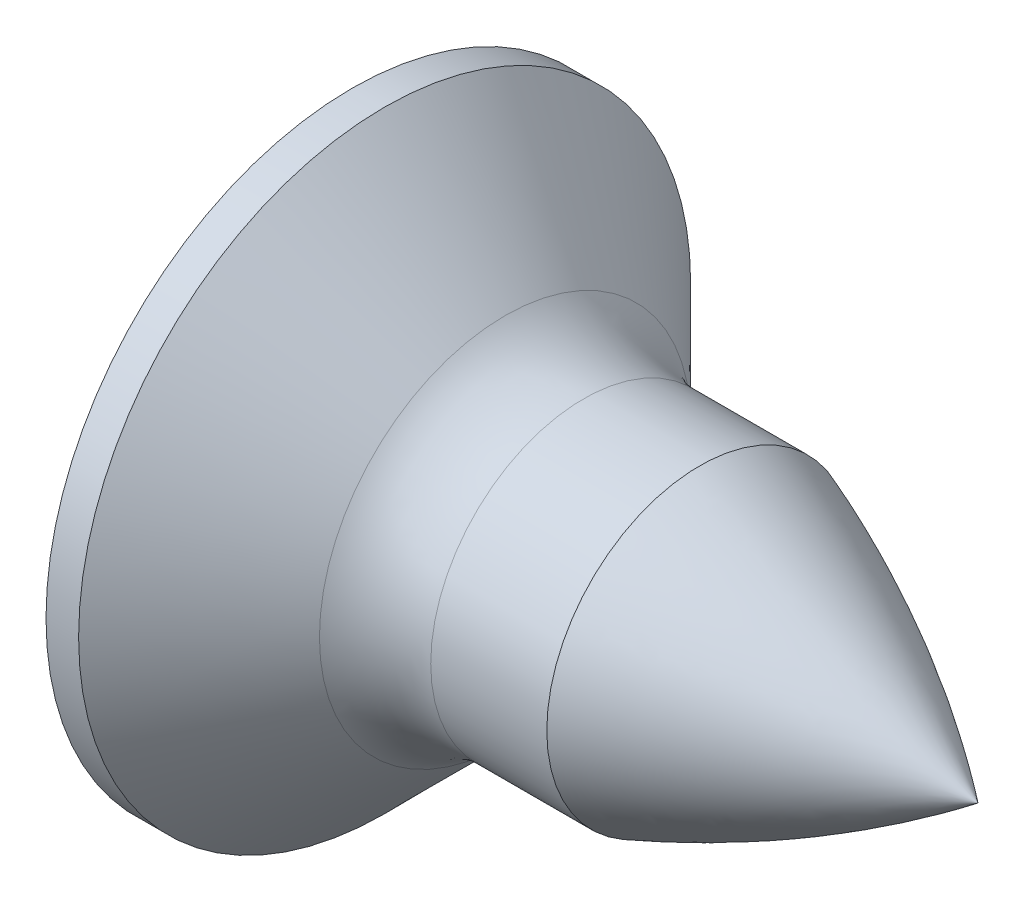
SolidWorks part; units mm, degrees
ref_plane "Front" through (0, 0, 0) normal (0, 0, 1) x (1, 0, 0)
ref_plane "Top" through (0, 0, 0) normal (0, 1, 0) x (1, 0, 0)
ref_plane "Right" through (0, 0, 0) normal (1, 0, 0) x (0, 0, -1)
sketch "Sketch1" plane through (0, 0, 0) normal (0, 0, 1) x (1, 0, 0)
  line L0 (-96.3852, 0) -> (11.3165, 0) construction
  line L1 (4.5, 0) -> (4.5, 1.1)
  line L2 (4.5, 1.1) -> (1.6657, 1.1)
  line L3 (1.9, 0.5946) -> (1.9, -0.97) construction
  line L4 (0.2343, 2.2) -> (0, 2.2)
  line L5 (4.5, 0) -> (0, 0)
  line L6 (1.1, 1.3343) -> (0.2343, 2.2)
  line L7 (0, 2.2) -> (0, 0)
  arc A0 (1.6657, 1.1) -> (1.1, 1.3343) centre (1.6657, 1.9) cw
  dimension "D1" = 45
  dimension "l" = 4.5
  dimension "k" = 1.1
revolve "Base" add sketch "Sketch1" angle 360 about L0
cosmetic thread "ThreadCosmetic1" [suppressed] parameters "D1"=2.6, "D2"=1.2
sketch "Sketch2" plane through (0, -0.7629, -8.3818) normal (-1, 0, 0) x (0, 0, 1)
  line L0 (2.3136, 0.7629) -> (16.8132, 0.7629) construction
  line L1 (8.3818, 3.0086) -> (8.3818, -8.9204) construction
  line L2 (8.5818, 1.7629) -> (8.1818, 1.7629)
  line L3 (8.1818, 1.7629) -> (8.1818, 0.9629)
  line L4 (8.1818, 0.9629) -> (7.3818, 0.9629)
  line L5 (7.3818, 0.9629) -> (7.3818, 0.5629)
  line L6 (8.1818, 0.5629) -> (7.3818, 0.5629)
  line L7 (8.1818, -0.2371) -> (8.1818, 0.5629)
  line L8 (8.5818, -0.2371) -> (8.1818, -0.2371)
  line L9 (8.5818, -0.2371) -> (8.5818, 0.5629)
  line L10 (8.5818, 0.5629) -> (9.3818, 0.5629)
  line L11 (9.3818, 0.9629) -> (9.3818, 0.5629)
  line L12 (8.5818, 0.9629) -> (9.3818, 0.9629)
  line L13 (8.5818, 1.7629) -> (8.5818, 0.9629)
  point P5 (9.3818, 0.7629)
  point P11 (7.3818, 0.7629)
  point P15 (8.3818, -0.2371)
  point P20 (8.3818, 1.7629)
  dimension "D1" = 0.4
extrude "CrossRecess" cut sketch "Sketch2" against normal blind 0.95
draft "Draft1" type of draft neutral plane draft angle 30 faces to draft 4 face at (0.475, -1, 0) face at (0.475, 0, 1) face at (0.475, 0, -1) face at (0.475, 1, 0) neutral plane through (0, 2.2, 0) neutral plane normal (-1, 0, 0) parameters "D1"=30
sketch "Sketch3" plane through (0, 0.5965, -8.6549) normal (-1, 0, 0) x (0, 0, 1)
  line L0 (8.6549, -0.5965) -> (16.919, 7.6677) construction
  line L2 (8.8549, -0.3965) -> (8.8549, -0.1965)
  line L4 (8.8549, -0.1965) -> (9.522, 0.2707)
  line L5 (9.0549, -0.3965) -> (9.522, 0.2707)
  line L6 (8.8549, -0.3965) -> (9.0549, -0.3965)
  line L7 (8.4549, -0.3965) -> (8.2549, -0.3965)
  line L8 (8.2549, -0.3965) -> (7.7877, 0.2707)
  line L9 (8.4549, -0.1965) -> (7.7877, 0.2707)
  line L10 (8.4549, -0.3965) -> (8.4549, -0.1965)
  line L11 (8.4549, -0.7965) -> (8.4549, -0.9965)
  line L12 (8.4549, -0.9965) -> (7.7877, -1.4636)
  line L13 (8.2549, -0.7965) -> (7.7877, -1.4636)
  line L14 (8.4549, -0.7965) -> (8.2549, -0.7965)
  line L15 (8.8549, -0.7965) -> (9.0549, -0.7965)
  line L16 (9.0549, -0.7965) -> (9.522, -1.4636)
  line L17 (8.8549, -0.9965) -> (9.522, -1.4636)
  line L18 (8.8549, -0.7965) -> (8.8549, -0.9965)
  line L19 (2.5867, -0.5965) -> (17.0862, -0.5965) construction
  line L20 (8.8549, -0.3965) -> (9.6549, -0.3965) construction
  line L22 (8.6549, 11.2261) -> (8.6549, -1) construction
  line L23 (10.9249, -0.5965) -> (-2.2894, -0.5965) construction
  dimension "D3" = 0.2
  dimension "D2" = 10
  dimension "D1" = 45
extrude "Cut-Extrude2" [suppressed] cut sketch "Sketch3" against normal up to surface (5.2 mm away) up to face at (0.95, 0, 0)
sketch "Sketch4" plane through (0, 0, 0) normal (0, 1, 0) x (1, 0, 0)
  line L0 (33.3282, 0) -> (18.3612, 0) construction
  line L2 (2.9, -1.1) -> (3.7, -1.1)
  line L3 (3.7, -1.1) -> (4.5, -0.9)
  line L5 (4.5, -1.1) -> (4.5, 1.1) construction
  line L6 (2.9, -1.1) -> (2.9, -1.6)
  line L7 (2.9, -1.6) -> (4.5, -1.6)
  line L8 (4.5, -1.6) -> (4.5, -0.9)
  point P15 (3.7, -1.1)
  dimension "D2" = 0.8
  dimension "D4" = 0.5
  dimension "D1" = 2.2
  dimension "D3" = 0.2
revolve "Cut-Revolve1" [suppressed] cut sketch "Sketch4" angle 360 about L0
sketch "Sketch5" plane through (0, 0, 0) normal (0, 1, 0) x (1, 0, 0)
  line L0 (34.7407, 0) -> (11.4121, 0) construction
  line L2 (4.5, -1.1) -> (4.5, 1.1) construction
  line L3 (4.5, 0) -> (2.5, -1.1) construction
  line L6 (4.5, 0) -> (5, 0)
  line L7 (2.5, -1.1) -> (4.5, -1.1)
  line L8 (5, 0) -> (5, -1.1)
  line L9 (5, -1.1) -> (4.5, -1.1)
  arc A0 (4.5, 0) -> (2.5, -1.1) centre (-0.3159, 6.388) cw
  dimension "D1" = 8
  dimension "D3" = 2.2
  dimension "D2" = 0.5
revolve "Cut-Revolve6" cut sketch "Sketch5" angle 360 about L0
sketch "Sketch6" plane through (0, 0, 0) normal (0, 0, 1) x (1, 0, 0)
  line L0 (1.65, 1.6) -> (2.15, 1.6)
  line L1 (2.15, 1.6) -> (2.15, 1.1)
  line L2 (2.15, 1.1) -> (1.9, 0.667)
  line L3 (1.9, 0.667) -> (1.65, 1.1)
  line L4 (1.65, 1.1) -> (1.65, 1.6)
  line L5 (0, 0) -> (5.5511, 0) construction
  line L7 (1.1, 1.3343) -> (1.1, -1.3343) construction
  dimension "D2" = 0.8
  dimension "D1" = 0.5
  dimension "D3" = 2.2
revolve "Cut-Revolve10" [suppressed] cut sketch "Sketch6" angle 360 about L5
pattern_linear "LPattern10" [suppressed] count 4 spacing 0.6 along (1, 0, 0) of bodies 110
equation "\"D3@Sketch4\" = \"yf@Sketch4\" / 8"
equation "\"D2@ThreadCosmetic1\" = \"st@Sketch1\" - 1"
equation "\"D1@Sketch5\" = \"yc@Sketch5\" * 4"
equation "\"D3@Sketch5\" = \"st@Sketch1\""
equation "\"D2@Sketch4\" = \"yf@Sketch4\" / 2"
equation "\"D1@Sketch2\" = \"m@Sketch2\" / 5"
equation "\"D1@Sketch4\" = \"st@Sketch1\""
equation "\"D1@ThreadCosmetic1\" = \"l@Sketch1\" - \"k@Sketch1\" - \"a@Sketch1\""
equation "\"D3@Sketch3\" = \"m@Sketch2\" / 10"
equation "\"D1@Sketch6\" = (  \"st@Sketch1\" - \"D2@ThreadCosmetic1\" )  / 2"
equation "\"D2@Sketch6\" = \"a@Sketch1\""
equation "\"D3@LPattern10\" = \"D1@Sketch6\" * 1.2"
equation "\"D1@LPattern10\" = \"D1@ThreadCosmetic1\" / \"D3@LPattern10\" "
equation "\"D3@Sketch6\" = \"st@Sketch1\""
